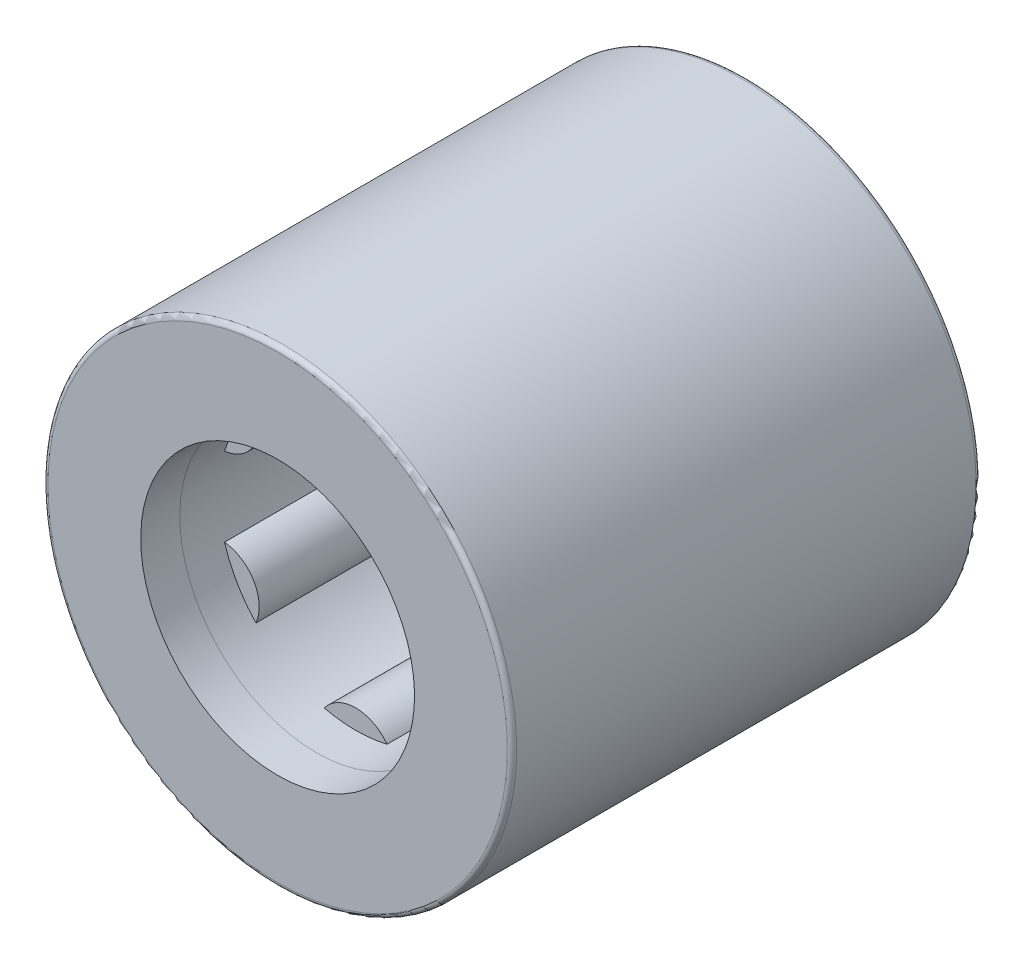
SolidWorks part; units mm, degrees
ref_plane "Front Plane" through (0, 0, 0) normal (0, 0, 1) x (1, 0, 0)
ref_plane "Top Plane" through (0, 0, 0) normal (0, 1, 0) x (1, 0, 0)
ref_plane "Right Plane" through (0, 0, 0) normal (1, 0, 0) x (0, 0, -1)
sketch "Sketch1" plane through (0, 0, 0) normal (1, 0, 0) x (0, 0, -1)
  line L0 (-6, 0) -> (6, 0) construction
  line L1 (0, 0) -> (0, 6) construction
  line L2 (-6, 0) -> (-6, 6) construction
  line L3 (-6, 6) -> (6, 6)
  line L4 (6, 6) -> (6, 0) construction
  line L5 (6, 0) -> (5.0017, 0) construction
  line L6 (5.0017, 0) -> (5.0017, 5.0017) construction
  line L7 (5.0017, 5.0017) -> (-5.0017, 5.0017)
  line L8 (-5.0017, 5.0017) -> (-5.0017, 0) construction
  line L9 (-5.0017, 0) -> (-6, 0) construction
  line L10 (-6, 6) -> (-6, 3.5042)
  line L11 (-6, 3.5042) -> (-5.0017, 3.5042)
  line L12 (-5.0017, 3.5042) -> (-5.0017, 5.0017)
  line L13 (5.0017, 6) -> (5.0017, 5.0017) construction
  line L14 (5.0017, 5.0017) -> (5.0017, 3.5042)
  line L15 (5.0017, 3.5042) -> (6, 3.5042)
  line L16 (6, 3.5042) -> (6, 6)
  line L17 (5.0017, 5.0017) -> (5.0017, 4.0033) construction
  line L18 (5.0017, 4.0033) -> (5.0017, 3.005) construction
  line L19 (5.0017, -5.0017) -> (5.0017, -4.0033) construction
  line L20 (5.0017, -6) -> (5.0017, -5.0017) construction
  line L21 (6, -3.5042) -> (6, -6) construction
  line L22 (5.0017, -3.5042) -> (6, -3.5042) construction
  line L23 (5.0017, -5.0017) -> (5.0017, -3.5042) construction
  line L24 (-5.0017, -3.5042) -> (-5.0017, -5.0017) construction
  line L25 (-6, -3.5042) -> (-5.0017, -3.5042) construction
  line L26 (-6, -6) -> (-6, -3.5042) construction
  line L27 (5.0017, -5.0017) -> (-5.0017, -5.0017) construction
  line L28 (-6, -6) -> (6, -6) construction
  point P5 (0, 3.005)
  dimension "Width" = 12
  dimension "OD" = 12
  dimension "Shaft Dia" = 6.01
revolve "Revolve1" add sketch "Sketch1" angle 360 about L0
sketch "Sketch2" plane through (0, 0, 0) normal (1, 0, 0) x (0, 0, -1)
  line L0 (5.0017, 5.0017) -> (-5.0017, 5.0017) construction
  line L1 (-4.0033, 4.0033) -> (4.0033, 4.0033) construction
  line L2 (-4.0033, 4.0033) -> (-4.0033, 5.0017) construction
  line L3 (-4.0033, 5.0017) -> (4.0033, 5.0017)
  line L4 (4.0033, 4.0033) -> (4.0033, 5.0017) construction
  line L5 (5.0017, 3.5042) -> (6, 3.5042) construction
  line L6 (-5.0017, 4.0033) -> (-4.0033, 4.0033) construction
  line L7 (4.0033, 4.0033) -> (5.0017, 4.0033) construction
  line L8 (-6, 3.5042) -> (-5.0017, 3.5042) construction
  line L9 (-4.0033, 4.2529) -> (-4.0033, 3.7538) construction
  line L10 (-5.0017, 4.0033) -> (-5.0017, 3.5042) construction
  line L11 (-4.0033, 5.0017) -> (-4.0033, 4.2529)
  line L12 (4.0033, 5.0017) -> (4.0033, 4.2529)
  line L13 (4.0033, 4.2529) -> (-4.0033, 4.2529)
  line L14 (0, 5.0017) -> (0, 3.005) construction
  line L15 (-5.0017, 3.5042) -> (-5.0017, 5.0017) construction
  line L16 (-4.0033, 3.7538) -> (-5.0017, 3.7538) construction
  line L17 (0, 0) -> (6, 0) construction
  line L18 (6, -6) -> (6, 6) construction
  line L19 (-4.0033, -3.7538) -> (-5.0017, -3.7538) construction
  line L20 (0, -5.0017) -> (0, -3.005) construction
  line L21 (-5.0017, -4.0033) -> (-5.0017, -3.5042) construction
  line L22 (-4.0033, -4.2529) -> (-4.0033, -3.7538) construction
  line L23 (4.0033, -4.0033) -> (5.0017, -4.0033) construction
  line L24 (-5.0017, -4.0033) -> (-4.0033, -4.0033) construction
  line L25 (4.0033, -4.0033) -> (4.0033, -5.0017) construction
  line L26 (-4.0033, -4.0033) -> (-4.0033, -5.0017) construction
  line L27 (-4.0033, -4.0033) -> (4.0033, -4.0033) construction
  line L28 (4.0033, -4.2529) -> (-4.0033, -4.2529) construction
  line L29 (4.0033, -5.0017) -> (4.0033, -4.2529) construction
  line L30 (-4.0033, -5.0017) -> (-4.0033, -4.2529) construction
  line L31 (-4.0033, -5.0017) -> (4.0033, -5.0017) construction
  line L32 (-5.0017, 5.0017) -> (-5.0017, 0) construction
  point P16 (0, 4.0033)
revolve "Revolve2" add sketch "Sketch2" angle 360 about L1
sketch "Sketch3" plane through (0, 0, 0) normal (1, 0, 0) x (0, 0, -1)
  line L0 (5.0017, 5.0017) -> (5.0017, 3.5042) construction
  line L1 (-5.0017, 4.0033) -> (5.0017, 4.0033)
  line L2 (-5.0017, 4.0033) -> (-5.0017, 4.2529)
  line L3 (-5.0017, 4.2529) -> (5.0017, 4.2529)
  line L4 (5.0017, 4.0033) -> (5.0017, 4.2529)
  line L5 (0, 0) -> (6, 0) construction
  line L6 (6, -6) -> (6, 6) construction
  line L7 (5.0017, -4.0033) -> (5.0017, -4.2529) construction
  line L8 (-5.0017, -4.2529) -> (5.0017, -4.2529) construction
  line L9 (-5.0017, -4.0033) -> (-5.0017, -4.2529) construction
  line L10 (-5.0017, -4.0033) -> (5.0017, -4.0033) construction
revolve "Revolve3" add sketch "Sketch3" angle 360 about L1
ref_axis "Axis1" through (0, 0, -6) along (0, 0, 1)
pattern_circular "CirPattern1" count 6 every 60 about axis through (0, 0, -6) along (0, 0, 1) of bodies 167 166
fillet "Fillet1" radius 0.12 2 edges at (0, -6, -6) (0, -6, 6)
sketch "Sketch4" plane through (0, 0, 0) normal (1, 0, 0) x (0, 0, -1)
  line L0 (-0.4992, 6) -> (0, 5.5008)
  line L1 (-6, 6) -> (6, 6) construction
  line L2 (0, 0) -> (0, 6) construction
  line L3 (0, 5.5008) -> (0.4992, 6)
  line L4 (0.4992, 6) -> (-0.4992, 6)
  line L5 (0, 6) -> (0, 5.0017) construction
revolve "Cut-Revolve1" [suppressed] cut sketch "Sketch4" angle 360 about L0
sketch "Sketch5" plane through (0, 0, -5.0017) normal (0, 0, 1) x (1, 0, 0)
  circle A0 centre (0, 0) radius 3.5042 construction
  circle A1 centre (0, 0) radius 5.0017
  circle A2 centre (0, 0) radius 5.0017 construction
  circle A3 centre (0, 0) radius 3.5042
  circle A4 centre (0, 0) radius 5.1017
  dimension "D1" = 0
  dimension "D2" = 0.1
extrude "Boss-Extrude1" add sketch "Sketch5" along normal up to surface (10.0033 mm away) separate body up to face at (0, -5.0017, 5.0017)
revolve "Cut-Revolve3" cut sketch "Sketch2<4>" angle 360 about L1
sketch "Sketch2<4>" plane through (0, 0, 0) normal (1, 0, 0) x (0, 0, -1) same geometry as "Sketch2"
pattern_circular "CirPattern2" count 6 over 360 about axis through (0, 0, 19.4314) along (0, 0, -1) of "Cut-Revolve3"
sketch "Sketch7" [suppressed] plane through (0, 0, 0) normal (1, 0, 0) x (0, 0, -1)
  line L0 (-0.8333, 20) -> (-0.8333, 19.1667)
  line L1 (-0.8333, 20) -> (-0.8333, -20) construction
  line L2 (-0.8333, 19.1667) -> (0.8333, 19.1667)
  line L3 (0.8333, 20) -> (0.8333, -20) construction
  line L4 (0.8333, 19.1667) -> (0.8333, 20)
  line L5 (0.8333, 20) -> (-0.8333, 20)
  dimension "D1" = 1.6667
revolve "Cut-Revolve4" [suppressed] cut sketch "Sketch7" angle 360
sketch "Sketch8" plane through (0, 0, 0) normal (1, 0, 0) x (0, 0, -1)
  circle A0 centre (0, 0) radius 0.4167
  dimension "D1" = 0.8333
extrude "Cut-Extrude2" [suppressed] cut sketch "Sketch8" along normal through all
equation "\"Angle@CirPattern1\" = 360/\"Rollers@CirPattern1\""
equation "\"Rollers@CirPattern1\" = \"OD@Sketch1\"*.5"
equation "\"D1@Fillet1\" = \"OD@Sketch1\"*.01"
equation "\"D1@CirPattern2\"= \"Rollers@CirPattern1\""
equation "\"D1@Sketch8\"=\"D1@Sketch7\" * .5"
